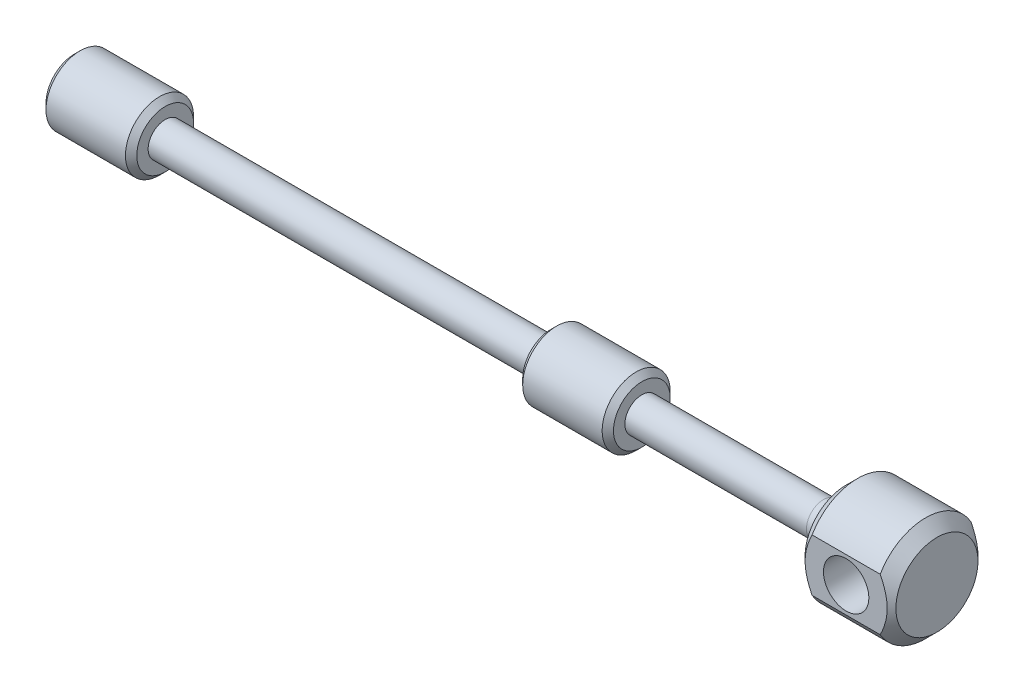
SolidWorks part; units mm, degrees
ref_plane "Front Plane" through (0, 0, 0) normal (0, 0, 1) x (1, 0, 0)
ref_plane "Top Plane" through (0, 0, 0) normal (0, 1, 0) x (1, 0, 0)
ref_plane "Right Plane" through (0, 0, 0) normal (1, 0, 0) x (0, 0, -1)
sketch "Sketch1" plane through (0, 0, 0) normal (1, 0, 0) x (0, 0, -1)
  circle A0 centre (0, 0) radius 1.5
  dimension "D1" = 3
extrude "Boss-Extrude1" add sketch "Sketch1" along normal mid plane 76
sketch "Sketch2" plane through (-38, 0, 0) normal (-1, 0, 0) x (0, 0, 1)
  circle A0 centre (0, 0) radius 3
  dimension "D1" = 6
extrude "Boss-Extrude2" add sketch "Sketch2" against normal blind 8
extrude "Boss-Extrude3" add sketch "Sketch2<2>" along normal blind 8 from offset 50 offset against normal yes
sketch "Sketch2<2>" plane through (-38, 0, 0) normal (-1, 0, 0) x (0, 0, 1) same geometry as "Sketch2"
chamfer "Chamfer1" distance 0.5 angle 45 4 edges at (12, 0, 3) (4, 0, 3) (-38, 0, 3) (-30, 0, 3)
sketch "Sketch3" plane through (38, 0, 0) normal (1, 0, 0) x (0, 0, -1)
  circle A0 centre (0, 0) radius 4.6174
extrude "Boss-Extrude4" add sketch "Sketch3" against normal blind 8
sketch "Sketch4" plane through (38, 0, 0) normal (1, 0, 0) x (0, 0, -1)
  line L0 (-4, 2.3065) -> (-4, -2.3065)
  line L1 (4, 2.3065) -> (4, -2.3065)
  arc A0 (4, -2.3065) -> (4, 2.3065) centre (0, 0) ccw
  circle A1 centre (0, 0) radius 4.6174
  arc A2 (-4, 2.3065) -> (-4, -2.3065) centre (0, 0) ccw
  dimension "D2" = 4
  dimension "D3" = 4
  dimension "D1" = 0
extrude "Cut-Extrude1" cut sketch "Sketch4" against normal blind 8
sketch "Sketch5" plane through (0, 0, 4) normal (0, 0, 1) x (1, 0, 0)
  line L0 (34, -2.3065) -> (34, 2.3065) construction
  line L1 (30, -2.3065) -> (38, -2.3065) construction
  line L2 (30, 2.3065) -> (38, 2.3065) construction
  circle A0 centre (34, 0) radius 2
  dimension "D1" = 4
extrude "Cut-Extrude2" cut sketch "Sketch5" against normal through all
chamfer "Chamfer2" distance 1 angle 45 2 edges at (38, -4.6174, 0) (30, -4.6174, 0)
fillet "Fillet1" radius 2 1 edges at (30, 0, -1.5)
